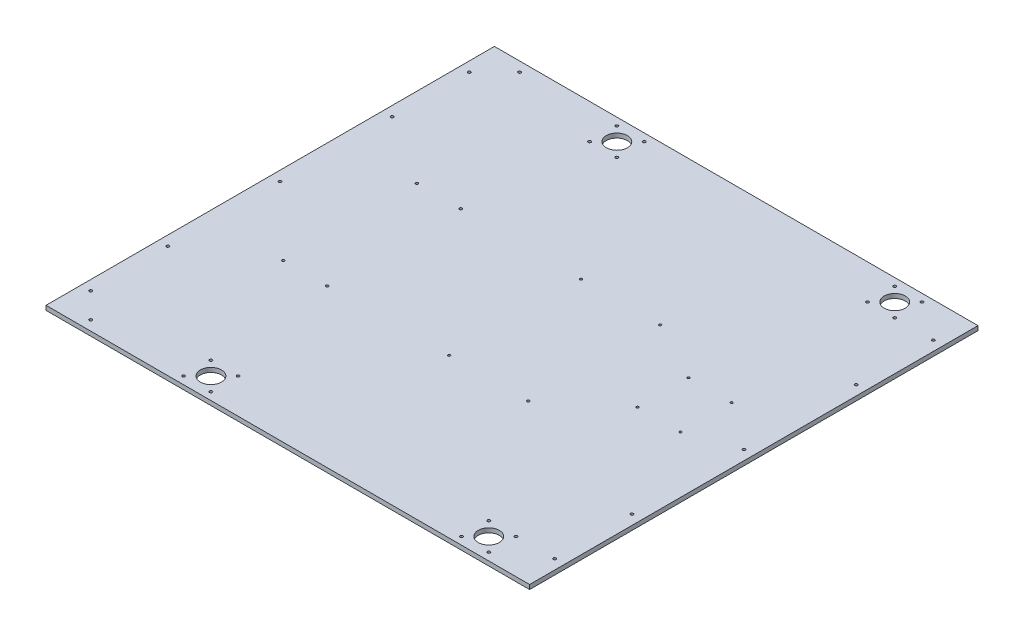
SolidWorks part; units mm, degrees
ref_plane "Front Plane" through (0, 0, 0) normal (0, 0, 1) x (1, 0, 0)
ref_plane "Top Plane" through (0, 0, 0) normal (0, 1, 0) x (1, 0, 0)
ref_plane "Right Plane" through (0, 0, 0) normal (1, 0, 0) x (0, 0, -1)
sketch "Sketch1" plane through (0, 0, 0) normal (1, 0, 0) x (0, 0, -1)
  line L0 (0, 0) -> (-510, 0)
  line L1 (-510, 0) -> (-510, 5)
  line L2 (-510, 5) -> (0, 5)
  line L6 (0, 5) -> (0, 0)
  dimension "D1" = 510
  dimension "D2" = 5
extrude "Boss-Extrude1" add sketch "Sketch1" along normal blind 550
sketch "BotthomHoles-Sketch2" plane through (0, 5, 0) normal (0, 1, 0) x (1, 0, 0)
  line L0 (550, -3.175) -> (0, -3.175) construction
  line L2 (550, 0) -> (550, -510) construction
  line L3 (550, 0) -> (0, 0) construction
  line L4 (550, -510) -> (0, -510) construction
  line L7 (0, 0) -> (0, -510) construction
  line L8 (550, 0) -> (550, -510) construction
  circle A0 centre (479.425, -24.175) radius 12
  circle A2 centre (463.925, -8.675) radius 1.5875
  circle A3 centre (494.925, -8.675) radius 1.5875
  circle A6 centre (463.925, -39.675) radius 1.5875
  circle A7 centre (494.925, -39.675) radius 1.5875
  circle A8 centre (39.6875, -11.1125) radius 1.5875
  circle A10 centre (178.925, -39.675) radius 1.5875
  circle A11 centre (147.925, -39.675) radius 1.5875
  circle A12 centre (178.925, -8.675) radius 1.5875
  circle A13 centre (147.925, -8.675) radius 1.5875
  circle A14 centre (163.425, -24.175) radius 12
  circle A15 centre (39.6875, -498.8875) radius 1.5875
  circle A16 centre (147.925, -501.325) radius 1.5875
  circle A17 centre (178.925, -501.325) radius 1.5875
  circle A18 centre (147.925, -470.325) radius 1.5875
  circle A19 centre (178.925, -470.325) radius 1.5875
  circle A20 centre (463.925, -470.325) radius 1.5875
  circle A21 centre (463.925, -501.325) radius 1.5875
  circle A22 centre (494.925, -470.325) radius 1.5875
  circle A23 centre (494.925, -501.325) radius 1.5875
  circle A25 centre (163.425, -485.825) radius 12
  circle A26 centre (479.425, -485.825) radius 12
  circle A27 centre (11.1125, -39.6875) radius 1.5875
  circle A28 centre (11.1125, -127.5) radius 1.5875
  circle A29 centre (11.1125, -255) radius 1.5875
  circle A30 centre (11.1125, -382.5) radius 1.5875
  circle A31 centre (11.1125, -470.3125) radius 1.5875
  circle A32 centre (538.8875, -470.3125) radius 1.5875
  circle A33 centre (538.8875, -382.5) radius 1.5875
  circle A34 centre (538.8875, -255) radius 1.5875
  circle A35 centre (538.8875, -127.5) radius 1.5875
  circle A36 centre (538.8875, -39.6875) radius 1.5875
  dimension "D9" = 3.175
  dimension "D10" = 24
  dimension "D13" = 3.175
  dimension "D29" = 3.175
  dimension "D2" = 8.675
  dimension "D5" = 15.5
  dimension "D6" = 31
  dimension "D7" = 15.5
  dimension "D8" = 31
  dimension "D11" = 21
  dimension "D12" = 39.6875
  dimension "D15" = 31
  dimension "D16" = 15.5
  dimension "D17" = 316
  dimension "D3" = 70.575
  dimension "D4" = 11.1125
  dimension "D18" = 8.675
  dimension "D19" = 15.5
  dimension "D20" = 31
  dimension "D21" = 11.1125
  dimension "D22" = 39.6875
  dimension "D23" = 39.6875
  dimension "D24" = 127.5
  dimension "D25" = 127.5
  dimension "D26" = 127.5
  dimension "D27" = 11.1125
  dimension "D28" = 11.1125
extrude "BottomHoles-Cut-Extrude1" cut sketch "BotthomHoles-Sketch2" against normal through all
sketch "BottomPSUHolesSketch2" plane through (0, 5, 0) normal (0, 1, 0) x (1, 0, 0)
  line L0 (0, 0) -> (0, -510) construction
  line L1 (550, 0) -> (0, 0) construction
  line L2 (550, -510) -> (0, -510) construction
  circle A0 centre (90.8, -179) radius 1.5
  circle A1 centre (140.8, -179) radius 1.5
  circle A2 centre (90.8, -331) radius 1.5
  circle A3 centre (140.8, -331) radius 1.5
  dimension "D6" = 3
  dimension "D1" = 152
  dimension "D2" = 50
  dimension "D3" = 90.8
  dimension "D4" = 179
  dimension "D5" = 179
extrude "BottomPSUHolesCut-Extrude1" cut sketch "BottomPSUHolesSketch2" against normal through all
sketch "BottomMainboardHolesSketch2" plane through (0, 5, 0) normal (0, 1, 0) x (1, 0, 0)
  line L0 (550, 0) -> (0, 0) construction
  line L1 (0, 0) -> (0, -510) construction
  line L2 (550, 0) -> (550, -510) construction
  line L3 (550, -510) -> (0, -510) construction
  circle A0 centre (278.5, -180) radius 1.35
  circle A1 centre (368.5, -180) radius 1.35
  circle A2 centre (278.5, -330) radius 1.35
  circle A3 centre (368.5, -330) radius 1.35
  circle A4 centre (436.7, -216) radius 1.35
  circle A5 centre (485.7, -216) radius 1.35
  circle A6 centre (436.7, -274) radius 1.35
  circle A7 centre (485.7, -274) radius 1.35
  dimension "D6" = 2.7
  dimension "D7" = 2.7
  dimension "D1" = 90
  dimension "D2" = 150
  dimension "D3" = 180
  dimension "D4" = 58
  dimension "D5" = 49
  dimension "D8" = 216
  dimension "D9" = 278.5
  dimension "D10" = 64.3
  dimension "D11" = 236
extrude "BottomMainboardHolesCut-Extrude1" cut sketch "BottomMainboardHolesSketch2" against normal through all
equation "\"LowerRailWidth\"= 2.00in"
equation "\"RailThickness\"= .125in'Spec"
equation "\"StepperHoleDiameter\"= 24mm"
equation "\"StepperMountingHoleDiameter\"= 3.175mm"
equation "\"SideRailLength\"= 550mm"
equation "\"StepperMountingHoleDistance\"= 31mm'Spec"
equation "\"StepperMountingHoleOffsetFromLeftOrRightSide\"= \"StepperMountingHoleOffsetFromItsSide\" + \"RailThickness\""
equation "\"HoleOffsetFromEdge\"= \"RailThickness\" * 2.5"
equation "\"HoleOffsetFromSide\"= \"RailThickness\" * 3.5"
equation "\"StepperMountingHoleOffsetFromItsSide\"= 5.5mm'Spec"
equation "\"FasteningHoleDiameter\"= .125in"
equation "\"D2@BotthomHoles-Sketch2\" = \"StepperMountingHoleOffsetFromLeftOrRightSide\""
equation "\"D5@BotthomHoles-Sketch2\" = \"StepperMountingHoleDistance\" / 2"
equation "\"D6@BotthomHoles-Sketch2\" = \"StepperMountingHoleDistance\""
equation "\"D7@BotthomHoles-Sketch2\" = \"StepperMountingHoleDistance\" / 2"
equation "\"D8@BotthomHoles-Sketch2\" = \"StepperMountingHoleDistance\""
equation "\"D9@BotthomHoles-Sketch2\" = \"StepperMountingHoleDiameter\""
equation "\"D10@BotthomHoles-Sketch2\" = \"StepperHoleDiameter\""
equation "\"D1@Boss-Extrude1\"=\"SideRailLength\""
equation "\"BedThirdSize\"= 70mm"
equation "\"BedInnerSquareWidth\"= \"BedThirdSize\" * 3'Equals 210"
equation "\"BedInnerSquareLength\"= \"BedInnerSquareWidth\""
equation "\"BedLWidth\"= \"BedThirdSize\"'Equals 70"
equation "\"BedLength\" = \"BedInnerSquareLength\" + \"BedLWidth\" * 2 + \"BedIncreasedByLength\"'Equals 350"
equation "\"DistanceBetweenFrontToBackStepperHoles\"= \"BedLength\" - \"DistanceFromBedFrontToFirstLeftStepperHole\"'Equals 316"
equation "\"DistanceFromBedFrontToFirstLeftStepperHole\"= \"LeadScrewNutPadSize\" + 10mm'Equals 34"
equation "\"DistanceFromFrontSideToBedFront\"= \"RailThickness\" + \"BeltTensionerDepth\" + 10mm'Equals 36.575"
equation "\"20TGT2PulleyDiameter\"= 17.9mm'Spec"
equation "\"BeltTensionerBackWallThickness\"= 4mm"
equation "\"BeltTensionerSpaceBetweenPulleyAndWall\"= 1.5mm"
equation "\"BeltTensionerInnerDepth\"= \"20TGT2PulleyDiameter\" + \"BeltTensionerSpaceBetweenPulleyAndWall\""
equation "\"BeltTensionerDepth\"= \"BeltTensionerBackWallThickness\" + \"BeltTensionerInnerDepth\"'Equals 23.4"
equation "\"BedIncreasedByLength\"= 0mm"
equation "\"LowerCornerBlockWidth\"= \"LowerRailWidth\" - \"RailThickness\" * 2'Room for left front stepper"
equation "\"D12@BotthomHoles-Sketch2\"=\"CornerEnclosureOffset\""
equation "\"D13@BotthomHoles-Sketch2\"=\"FasteningHoleDiameter\""
equation "\"CornerEnclosureOffset\"= \"LowerCornerBlockWidth\" - \"HoleOffsetFromEdge\" + \"RailThickness\""
equation "\"LowerCornerBlockY1FromSide\"= \"HoleOffsetFromSide\""
equation "\"D15@BotthomHoles-Sketch2\"=\"StepperMountingHoleDistance\""
equation "\"D16@BotthomHoles-Sketch2\"=\"StepperMountingHoleDistance\"/2"
equation "\"D17@BotthomHoles-Sketch2\"=\"DistanceBetweenFrontToBackStepperHoles\""
equation "\"DistanceFromFrontSideToFirstLeftStepperHole\"= \"DistanceFromFrontSideToBedFront\" + \"DistanceFromBedFrontToFirstLeftStepperHole\"'Equals 70.575"
equation "\"LeadScrewNutMountingHoleFlangeDiameter\"= 22mm'Spec"
equation "\"LeadScrewNutPadSize\"= \"LeadScrewNutMountingHoleFlangeDiameter\" + 2mm'Equals 24"
equation "\"D3@BotthomHoles-Sketch2\"=\"DistanceFromFrontSideToFirstLeftStepperHole\""
equation "\"LowerEnclosureThickness\"= 5mm"
equation "\"FrontBackRailLength\"= 510mm"
equation "\"D4@BotthomHoles-Sketch2\"=\"LowerCornerBlockY1FromSide\""
equation "\"D1@Sketch1\"=\"FrontBackRailLength\""
equation "\"D18@BotthomHoles-Sketch2\"=\"StepperMountingHoleOffsetFromLeftOrRightSide\""
equation "\"D19@BotthomHoles-Sketch2\"=\"StepperMountingHoleDistance\"/2"
equation "\"D20@BotthomHoles-Sketch2\"=\"StepperMountingHoleDistance\""
equation "\"D21@BotthomHoles-Sketch2\"=\"LowerCornerBlockY1FromSide\""
equation "\"D22@BotthomHoles-Sketch2\"=\"CornerEnclosureOffset\""
equation "\"D23@BotthomHoles-Sketch2\"=\"CornerEnclosureOffset\""
equation "\"FrontOrBackEnclosureOffsets\"= \"FrontBackRailLength\" / 4"
equation "\"D24@BotthomHoles-Sketch2\"=\"FrontOrBackEnclosureOffsets\""
equation "\"D25@BotthomHoles-Sketch2\"=\"FrontOrBackEnclosureOffsets\""
equation "\"D26@BotthomHoles-Sketch2\"=\"FrontOrBackEnclosureOffsets\""
equation "\"D27@BotthomHoles-Sketch2\"=\"LowerCornerBlockY1FromSide\""
equation "\"D28@BotthomHoles-Sketch2\"=\"LowerCornerBlockY1FromSide\""
equation "\"D29@BotthomHoles-Sketch2\"=\"FasteningHoleDiameter\""
equation "\"D2@Sketch1\"=\"LowerEnclosureThickness\""
equation "\"24VPSUMountingHolesShortDistanceBetween\"= 50mm'Yours may differ"
equation "\"24VPSUMountingHolesLongDistanceBetween\"= 152mm'Yours may differ"
equation "\"24VPSUMountingHoleOffsetFromEitherSide\"= 30mm'Yours may differ"
equation "\"24VPSUMountingHoleOffsetFromEdge\"= \"24VPSUMountingHoleOffsetFromEitherSide\" + \"LowerRailWidth\" + 10mm'Yours may differ"
equation "\"24VPSUMountingHoleDiameter\"= 3mm'Yours may differ"
equation "\"D2@BottomPSUHolesSketch2\" = \"24VPSUMountingHolesShortDistanceBetween\""
equation "\"D1@BottomPSUHolesSketch2\" = \"24VPSUMountingHolesLongDistanceBetween\""
equation "\"D3@BottomPSUHolesSketch2\" = \"24VPSUMountingHoleOffsetFromEdge\""
equation "\"D4@BottomPSUHolesSketch2\" =  ( \"FrontBackRailLength\" - \"24VPSUMountingHolesLongDistanceBetween\" )  / 2"
equation "\"D6@BottomPSUHolesSketch2\" = \"24VPSUMountingHoleDiameter\""
equation "\"RPi4BoardLength\"= 85mm'Spec"
equation "\"RPi4BoardWidth\"= 56mm'Spec"
equation "\"RPi4BoardMountingHoleOffsetFromEdge\"= 3.5mm'Spec"
equation "\"RPi4BoardMountingHoleDiameter\"= 2.7mm'Spec"
equation "\"OctopusV1.1BoardLength\"= 160mm'Spec"
equation "\"OctopusV1.1BoardWidth\"= 100mm'Spec"
equation "\"OctopusV1.1BoardMountingHoleOffsetFromAllEdges\"= 3.5mm'Spec"
equation "\"OctopusV1.1BoardMountingHoleLengthDistanceBetween\"= 150mm'Spec"
equation "\"OctopusV1.1BoardMountingHoleWidthDistanceBetween\"= 90mm'Spec"
equation "\"D2@BottomMainboardHolesSketch2\" = \"OctopusV1.1BoardMountingHoleLengthDistanceBetween\""
equation "\"D3@BottomMainboardHolesSketch2\" =  ( \"FrontBackRailLength\" - \"OctopusV1.1BoardMountingHoleLengthDistanceBetween\" )  / 2"
equation "\"D4@BottomMainboardHolesSketch2\" = \"RPi4BoardMountingHoleLengthDistanceBetween\""
equation "\"D5@BottomMainboardHolesSketch2\"=\"RPi4BoardWidth\"- \"RPi4BoardMountingHoleOffsetFromEdge\" * 2"
equation "\"D6@BottomMainboardHolesSketch2\" = \"OctopusV1.1BoardMountingHoleDiameter\""
equation "\"D7@BottomMainboardHolesSketch2\" = \"RPi4BoardMountingHoleDiameter\""
equation "\"RPi4BoardMountingHoleLengthDistanceBetween\"= 58mm'Spec"
equation "\"OctopusV1.1BoardMountingHoleDiameter\"= 2.7mm'Spec"
equation "\"D1@BottomMainboardHolesSketch2\" = \"OctopusV1.1BoardMountingHoleWidthDistanceBetween\""
equation "\"D8@BottomMainboardHolesSketch2\" =  ( \"FrontBackRailLength\" - \"RPi4BoardLength\" )  / 2 + \"RPi4BoardMountingHoleOffsetFromEdge\""
equation "\"D9@BottomMainboardHolesSketch2\" = \"SideRailLength\" / 2 + \"OctopusV1.1BoardMountingHoleOffsetFromAllEdges\""
equation "\"D10@BottomMainboardHolesSketch2\" = \"LowerRailWidth\" + \"RPi4BoardMountingHoleOffsetFromEdge\" + 10mm"
